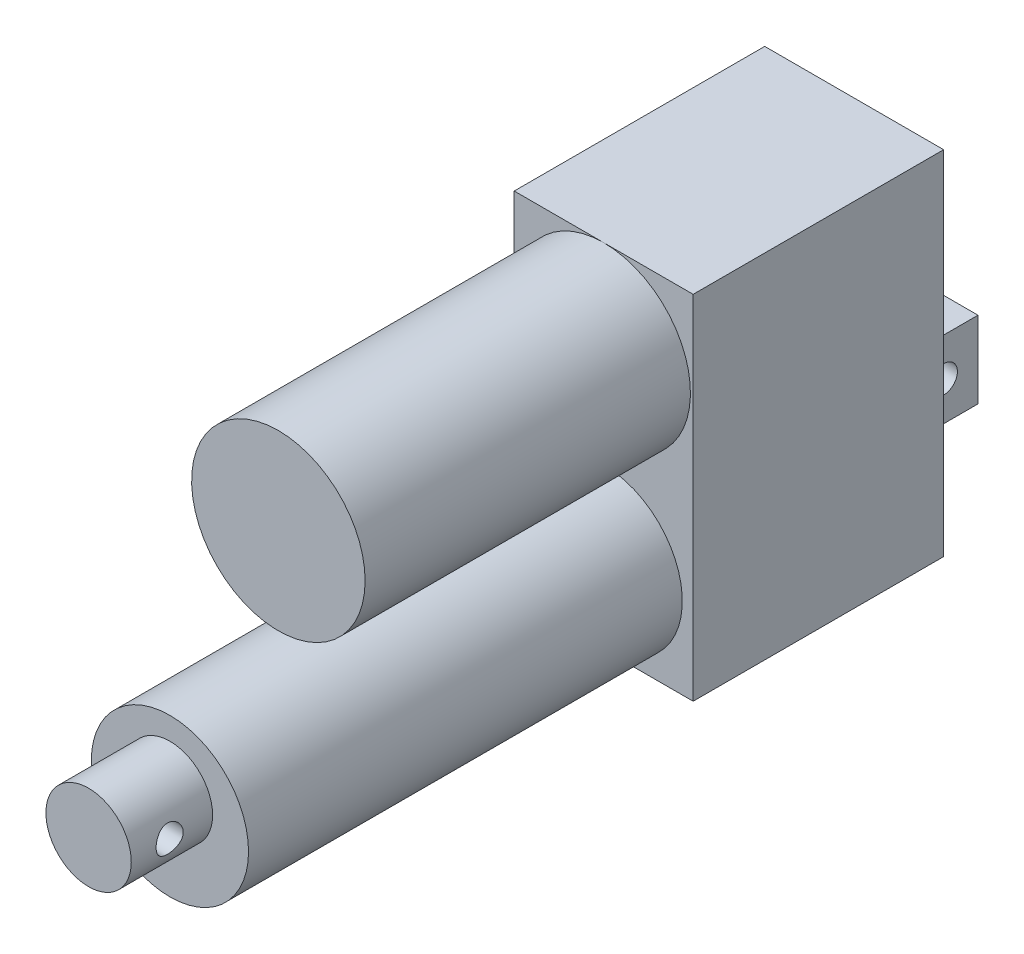
SolidWorks part; units mm, degrees
ref_plane "Front Plane" through (0, 0, 0) normal (0, 0, 1) x (1, 0, 0)
ref_plane "Top Plane" through (0, 0, 0) normal (0, 1, 0) x (1, 0, 0)
ref_plane "Right Plane" through (0, 0, 0) normal (1, 0, 0) x (0, 0, -1)
sketch "Sketch1" plane through (0, 0, 0) normal (0, 0, 1) x (1, 0, 0)
  line L0 (10.4363, 0) -> (-10.4363, 0) construction
  line L1 (-20.955, 0) -> (20.955, 0)
  line L2 (-20.955, 0) -> (-20.955, 82.55)
  line L3 (-20.955, 82.55) -> (20.955, 82.55)
  line L4 (20.955, 0) -> (20.955, 82.55)
  line L6 (0, -19.8313) -> (0, 19.8313) construction
  dimension "D1" = 82.55
  dimension "D2" = 41.91
  dimension "D3" = 20.955
extrude "Boss-Extrude1" add sketch "Sketch1" along normal blind 58.674
sketch "Sketch2" plane through (0, 0, 58.674) normal (0, 0, 1) x (1, 0, 0)
  line L0 (20.955, 82.55) -> (-20.955, 82.55) construction
  circle A0 centre (0, 62.23) radius 20.32
  dimension "D1" = 40.64
  dimension "D2" = 20.32
extrude "Boss-Extrude2" add sketch "Sketch2" along normal blind 76.2
sketch "Sketch3" plane through (0, 0, 58.674) normal (0, 0, 1) x (1, 0, 0)
  line L0 (0, -55) -> (0, 55) construction
  line L1 (55, 0) -> (-55, 0) construction
  circle A0 centre (0, 19.05) radius 18.415
  dimension "D1" = 36.83
  dimension "D2" = 19.05
extrude "Boss-Extrude3" add sketch "Sketch3" along normal blind 101.6
sketch "Sketch4" plane through (0, 0, 160.274) normal (0, 0, 1) x (1, 0, 0)
  line L0 (55, 0) -> (-55, 0) construction
  circle A0 centre (0, 22.225) radius 9.9949
  dimension "D2" = 19.9898
  dimension "D1" = 22.225
extrude "Boss-Extrude4" add sketch "Sketch4" along normal blind 19.05
ref_axis "Axis1" through (0, 22.225, 179.324) along (0, 0, -1)
sketch "Sketch6" plane through (0, 0, 0) normal (1, 0, 0) x (0, 0, -1)
  line L0 (-179.324, 22.225) -> (-160.274, 22.225) construction
  line L1 (-179.324, 32.2199) -> (-179.324, 12.2301) construction
  circle A0 centre (-170.324, 22.225) radius 3.175
  dimension "D2" = 6.35
  dimension "D1" = 9
extrude "Cut-Extrude1" cut sketch "Sketch6" against normal blind 19.05 and the other way blind 19.05
sketch "Sketch7" plane through (0, 0, 0) normal (0, 0, -1) x (-1, 0, 0)
  line L0 (0, 55) -> (0, -55) construction
  line L1 (-9, 15) -> (9, 15)
  line L2 (-9, 15) -> (-9, 33)
  line L3 (-9, 33) -> (9, 33)
  line L4 (9, 15) -> (9, 33)
  line L5 (55, 0) -> (-55, 0) construction
  dimension "D1" = 18
  dimension "D2" = 18
  dimension "D3" = 9
  dimension "D4" = 15
extrude "Boss-Extrude5" add sketch "Sketch7" along normal blind 20
sketch "Sketch8" plane through (-9, 0, 0) normal (-1, 0, 0) x (0, 0, 1)
  line L0 (0, -55) -> (0, 55) construction
  line L1 (-20, 15) -> (0, 15) construction
  circle A0 centre (-12, 24) radius 3.175
  dimension "D2" = 6.35
  dimension "D1" = 12
  dimension "D3" = 9
extrude "Cut-Extrude2" cut sketch "Sketch8" against normal blind 20 and the other way blind 20
